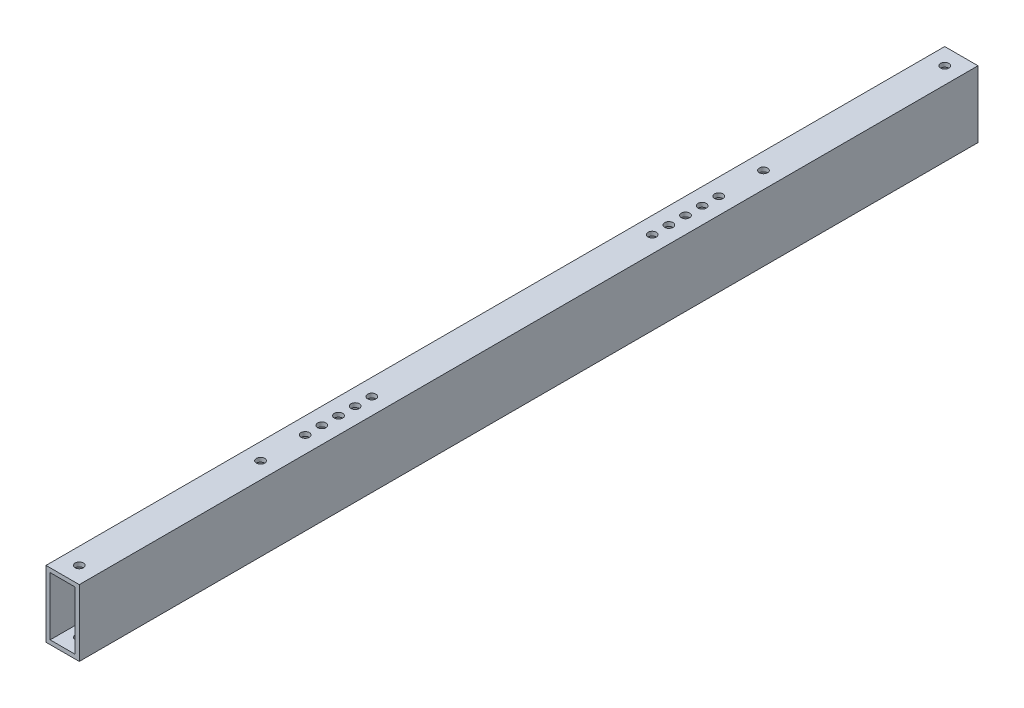
SolidWorks part; units mm, degrees
ref_plane "Front Plane" through (0, 0, 0) normal (0, 0, 1) x (1, 0, 0)
ref_plane "Top Plane" through (0, 0, 0) normal (0, 1, 0) x (1, 0, 0)
ref_plane "Right Plane" through (0, 0, 0) normal (1, 0, 0) x (0, 0, -1)
sketch "Sketch1" plane through (0, 0, 0) normal (0, 0, 1) x (1, 0, 0)
  line L0 (-9.525, 22.225) -> (9.525, 22.225)
  line L1 (-12.7, -25.4) -> (12.7, -25.4)
  line L2 (-12.7, -25.4) -> (-12.7, 25.4)
  line L3 (-12.7, 25.4) -> (12.7, 25.4)
  line L4 (12.7, -25.4) -> (12.7, 25.4)
  line L5 (-12.7, -25.4) -> (12.7, 25.4) construction
  line L6 (-12.7, 25.4) -> (12.7, -25.4) construction
  line L7 (9.525, -22.225) -> (9.525, 22.225)
  line L8 (-9.525, -22.225) -> (9.525, -22.225)
  line L9 (-9.525, -22.225) -> (-9.525, 22.225)
  point P0 (0, 0)
  dimension "D1" = 25.4
  dimension "D2" = 50.8
  dimension "D3" = 3.175
extrude "Boss-Extrude1" add sketch "Sketch1" along normal blind 685.8
sketch "Sketch2" plane through (0, 25.4, 0) normal (0, 1, 0) x (1, 0, 0)
  line L0 (0, -685.8) -> (0, 0) construction
  line L1 (12.7, -685.8) -> (-12.7, -685.8) construction
  line L2 (12.7, 0) -> (-12.7, 0) construction
  line L3 (-12.7, -342.9) -> (12.7, -342.9) construction
  line L4 (-12.7, -685.8) -> (-12.7, 0) construction
  line L5 (12.7, -685.8) -> (12.7, 0) construction
  circle A0 centre (0, -12.7) radius 3.175
  circle A1 centre (0, -151.0121) radius 3.175
  circle A2 centre (0, -534.7879) radius 3.175
  circle A3 centre (0, -673.1) radius 3.175
  circle A4 centre (0, -185.1063) radius 3.175
  circle A5 centre (0, -197.8063) radius 3.175
  circle A6 centre (0, -210.5063) radius 3.175
  circle A7 centre (0, -223.2063) radius 3.175
  circle A8 centre (0, -235.9063) radius 3.175
  circle A9 centre (0, -449.8937) radius 3.175
  circle A10 centre (0, -462.5937) radius 3.175
  circle A11 centre (0, -475.2937) radius 3.175
  circle A12 centre (0, -487.9937) radius 3.175
  circle A13 centre (0, -500.6937) radius 3.175
  dimension "D1" = 12.7
  dimension "D4" = 6.35
  dimension "D3" = 138.3121
  dimension "D5" = 172.4063
  dimension "D2" = 2
  dimension "D6" = 5
extrude "Cut-Extrude1" cut sketch "Sketch2" against normal through all
